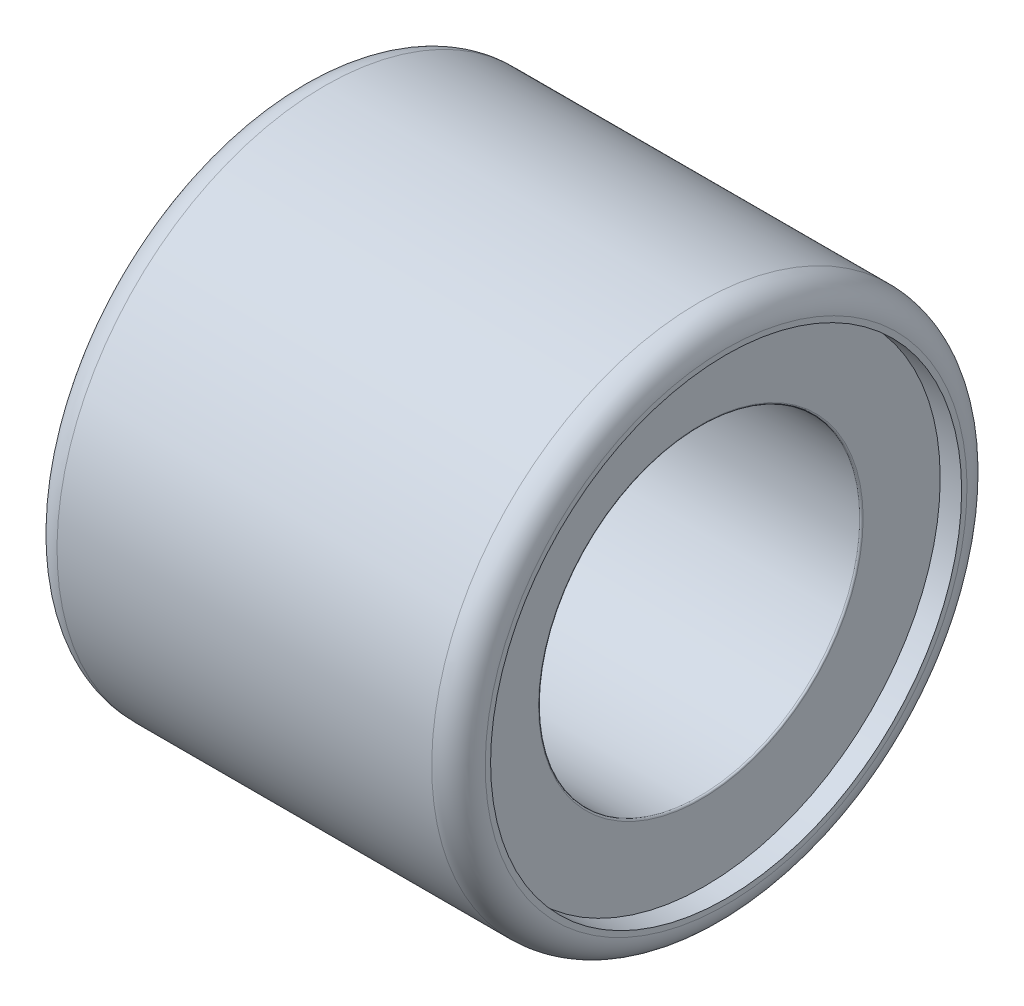
SolidWorks part; units mm, degrees
ref_plane "Plane1" through (0, 0, 0) normal (0, 0, 1) x (1, 0, 0)
ref_plane "Plane2" through (0, 0, 0) normal (0, 1, 0) x (1, 0, 0)
ref_plane "Plane3" through (0, 0, 0) normal (1, 0, 0) x (0, 0, -1)
other "Configuration Table"
sketch "Clipboard" plane through (0, 0, 0) normal (0, 0, 1) x (1, 0, 0)
  line L0 (-10, 0) -> (10, 0) construction
  line L1 (0, 0) -> (22.3471, -0.7804)
  line L2 (0, 0) -> (3.7977, 0.1326)
  line L3 (0, 0) -> (22.3471, -0.7804)
  line L4 (0, 0) -> (-6, -0.1047)
  dimension "BallCLRad" = 3.8
  dimension "Bore" = 6
sketch "InnRacSke" plane through (0, 0, 0) normal (0, 0, 1) x (1, 0, 0)
  line L0 (-3.6, 4.4) -> (-4, 4.4)
  line L1 (-4, 4.4) -> (-4, 4.5)
  line L2 (-3.5, 5) -> (3.5, 5)
  line L4 (4, 4.5) -> (4, 4.4)
  line L5 (4, 4.4) -> (3.6, 4.4)
  line L6 (3.6, 4.4) -> (3.6, 4.6)
  line L7 (3.6, 4.6) -> (-3.6, 4.6)
  line L8 (-3.6, 4.6) -> (-3.6, 4.4)
  line L9 (-31.75, 0) -> (31.75, 0) construction
  arc A0 (-4, 4.5) -> (-3.5, 5) centre (-3.5, 4.5) cw
  arc A2 (3.5, 5) -> (4, 4.5) centre (3.5, 4.5) cw
  dimension "D1" = 9.2
revolve "Race" add sketch "InnRacSke" angle 360 about L9 reverse direction yes
sketch "RolDetSke" plane through (0, 0, 0) normal (0, 0, 1) x (1, 0, 0)
  line L0 (-3.528, 4.5685) -> (-3.528, 3.8)
  line L1 (-3.528, 3.8) -> (3.528, 3.8)
  line L2 (3.528, 3.8) -> (3.528, 4.5685)
  line L3 (3.496, 4.6005) -> (-3.496, 4.6005)
  line L4 (-28.575, 3.8) -> (28.575, 3.8) construction
  arc A0 (3.528, 4.5685) -> (3.496, 4.6005) centre (3.496, 4.5685) ccw
  arc A1 (-3.496, 4.6005) -> (-3.528, 4.5685) centre (-3.496, 4.5685) ccw
  dimension "Roller_length" = 7.056
  dimension "Roller_diameter" = 1.601
revolve "RollerDetailed" [suppressed] add sketch "RolDetSke" angle 360 about L4 reverse direction yes
ref_axis "Axis1" through (-50, 0, 0) along (1, 0, 0)
sketch "CagSpiSke" plane through (0, 0, 0) normal (0, 0, 1) x (1, 0, 0)
  line L0 (3.8, 3.6399) -> (3.8, 3.9601)
  line L1 (3.8, 3.9601) -> (-3.8, 3.9601)
  line L2 (-3.8, 3.9601) -> (-3.8, 3.6399)
  line L3 (-3.8, 3.6399) -> (3.8, 3.6399)
  line L4 (-31.75, 0) -> (31.75, 0) construction
  dimension "D2" = 7.2798
  dimension "halfWidth" = 3.8
revolve "CageSpine" [suppressed] add sketch "CagSpiSke" angle 180.001 about L4
pattern_circular "RollersDetailed" [suppressed] count 2 every 180 about axis through (-50, 0, 0) along (1, 0, 0)
sketch "RolSimSke" plane through (0, 0, 0) normal (0, 0, 1) x (1, 0, 0)
  line L0 (-25.4, 0) -> (25.4, 0) construction
  line L2 (-3.496, 4.601) -> (3.496, 4.601)
  line L3 (-3.528, 4.569) -> (-3.528, 3.032)
  line L4 (-3.496, 3) -> (3.496, 3)
  line L5 (3.528, 4.569) -> (3.528, 3.032)
  arc A0 (-3.528, 3.032) -> (-3.496, 3) centre (-3.496, 3.032) ccw
  arc A1 (-3.496, 4.601) -> (-3.528, 4.569) centre (-3.496, 4.569) ccw
  arc A2 (3.528, 4.569) -> (3.496, 4.601) centre (3.496, 4.569) ccw
  arc A3 (3.496, 3) -> (3.528, 3.032) centre (3.496, 3.032) ccw
  point P10 (-3.528, 3)
  point P15 (3.528, 4.601)
  point P18 (3.528, 3)
  dimension "D1" = 0.032
  dimension "Bore" = 6
  dimension "Roller_length" = 7.056
  dimension "Roller_diameter" = 1.601
  dimension "halfWidth" = 3.528
revolve "RollersSimplified" add sketch "RolSimSke" angle 360 about L0
equation "\"BallCLRad@Clipboard\" =  ( \"D1@InnRacSke\" + \"Bore@Clipboard\" )  / 4"
equation "\"RollerCLRad@RolDetSke\" = \"BallCLRad@Clipboard\""
equation "\"halfCyl@InnRacSke\" = \"Cyl_Len@InnRacSke\" / 2"
equation "\"Roller_length@RolDetSke\" = \"Cyl_Len@InnRacSke\" * .98"
equation "\"halfLength@RolDetSke\" = \"Roller_length@RolDetSke\" / 2"
equation "\"Roller_diameter@RolDetSke\" =  ( \"D1@InnRacSke\" - \"Bore@Clipboard\" )  / 2 + .001"
equation "\"Roller_radius@RolDetSke\" = \"Roller_diameter@RolDetSke\" / 50"
equation "\"Cage_width@CagSpiSke\" =  ( \"Cyl_Len@InnRacSke\" + \"Width@InnRacSke\" )  / 2"
equation "\"halfWidth@CagSpiSke\" = \"Cage_width@CagSpiSke\" / 2"
equation "\"Cage_thickness@CagSpiSke\"  = \"Roller_diameter@RolDetSke\" / 5"
equation "\"D2@CagSpiSke\" =  \"RollerCLRad@RolDetSke\" * 2 - \"Cage_thickness@CagSpiSke\""
equation "\"Roller_length@RolSimSke\" = \"Cyl_Len@InnRacSke\" * .98"
equation "\"halfWidth@RolSimSke\" = \"Roller_length@RolSimSke\" / 2"
equation "\"D1@RolSimSke\" = \"Roller_radius@RolDetSke\""
equation "\"Roller_diameter@RolSimSke\" =  ( \"D1@InnRacSke\" - \"Bore@Clipboard\" )  / 2 + .001"
equation "\"Bore@RolSimSke\" = \"Bore@Clipboard\""
equation "\"Max_count@Clipboard\" = int( 3.14159265 / atn(( \"Roller_diameter@RolDetSke\" / 2) / sqr( \"RollerCLRad@RolDetSke\"  *  \"RollerCLRad@RolDetSke\" - ( \"Roller_diameter@RolDetSke\" / 2) *  ( \"Roller_diameter@RolDetSke\" / 2))))"
equation "\"Max_count@Clipboard\" = ((sgn( \"Max_count@Clipboard\" - \"Count@Clipboard\" )-1)*( \"Max_count@Clipboard\" - \"Count@Clipboard\" ))/-2+ \"Count@Clipboard\""
equation "\"Count@RollersDetailed\" = int( \"Show_count@Clipboard\" ) "
equation "\"Count@RollersDetailed\" = ((sgn( \"Count@RollersDetailed\" - \"Max_count@Clipboard\" )-1)*( \"Count@RollersDetailed\" - \"Max_count@Clipboard\" ))/-2+ \"Max_count@Clipboard\""
equation "\"Count@RollersDetailed\" = ((sgn( \"Count@RollersDetailed\" - \"Min_count@Clipboard\" )+1)*( \"Count@RollersDetailed\" - \"Min_count@Clipboard\"))/2 +\"Min_count@Clipboard\""
equation "\"Angle@RollersDetailed\" = 360.0 / \"Max_count@Clipboard\""
equation "\"Angle@CageSpine\" =  \"Angle@RollersDetailed\" * ( \"Count@RollersDetailed\" -1 + int( \"Count@RollersDetailed\" / \"Max_count@Clipboard\" ) )  + 0.001 -  int( \"Count@RollersDetailed\" / \"Max_count@Clipboard\" ) * 0.001"
equation "\"Angle@CageSpine\" =  \"Angle@CageSpine\" * int( \"Min_count@Clipboard\" / 2) + int(1 / \"Min_count@Clipboard\")  * 0.001"
